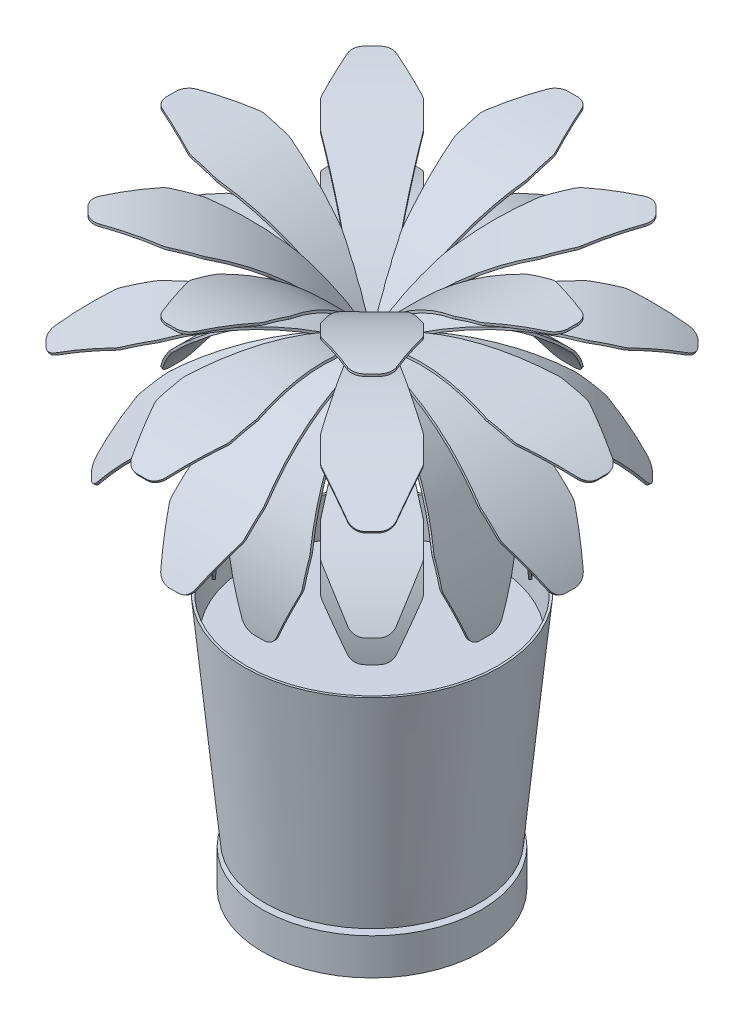
SolidWorks part; units mm, degrees
note: '?' marks a value the reader was unsure of.
material "Beech"
ref_plane "Front Plane" through (0, 0, 0) normal (0, 0, 1) x (1, 0, 0)
ref_plane "Top Plane" through (0, 0, 0) normal (0, 1, 0) x (1, 0, 0)
ref_plane "Right Plane" through (0, 0, 0) normal (1, 0, 0) x (0, 0, -1)
ref_axis "X-Axis" through (-88.99, 0, 0) along (1, 0, 0)?
ref_axis "Y-Axis" through (0, 55, 0) along (0, -1, 0)?
ref_axis "Z-Axis" through (0, 0, -88.99) along (0, 0, 1)?
sketch "Sketch1" plane through (0, 0, 0) normal (0, 0, 1) x (1, 0, 0)
  line L0 (0, 0) -> (0, 152.4)
  line L1 (87.3052, 177.8) -> (88.9, 177.8)
  line L2 (88.9, 177.8) -> (74.6125, 28.575)
  line L3 (74.6125, 28.575) -> (69.85, 28.575)
  line L4 (69.85, 28.575) -> (69.85, 25.4)
  line L5 (69.85, 25.4) -> (76.2, 25.4)
  line L6 (76.2, 25.4) -> (76.2, 0)
  line L7 (76.2, 0) -> (0, 0)
  line L8 (0, 0) -> (0, -76.2) construction
  line L9 (87.3052, 177.8) -> (84.8733, 152.4)
  line L10 (84.8733, 152.4) -> (0, 152.4)
  dimension "D1" = 25.4
  dimension "D2" = 177.8
  dimension "D3" = 152.4
  dimension "D4" = 6.35
  dimension "D5" = 3.175
  dimension "D6" = 1.5875
  dimension "D7" = 177.8
  dimension "D8" = 25.4
  dimension "D9" = 1.5875
revolve "Revolve1" add sketch "Sketch1" angle 360 about L8
sketch "Sketch3" plane through (0, 152.4, 0) normal (0, 1, 0) x (1, 0, 0)
  circle A0 centre (0, 0) radius 9.525
  dimension "D1" = 19.05
extrude "Boss-Extrude1" add sketch "Sketch3" along normal blind 177.8 draft 2 separate body
sketch "Sketch4" plane through (0, 0, 0) normal (0, 0, 1) x (1, 0, 0)
  line L0 (3.3161, 330.2) -> (-3.3161, 330.2) construction
  line L1 (77.1118, 190.5) -> (78.6993, 190.5)
  line L2 (0.846, 331.5433) -> (0, 330.2)
  line L3 (87.3052, 177.8) -> (-87.3052, 177.8) construction
  arc A0 (0, 330.2) -> (77.1118, 190.5) centre (-87.9882, 190.5) cw
  arc A1 (78.6993, 190.5) -> (0.846, 331.5433) centre (-87.9882, 190.5) ccw
  dimension "D2" = 165.1
  dimension "D1" = 1.5875
  dimension "D3" = 12.7
extrude "Boss-Extrude2" add sketch "Sketch4" along normal mid plane 50.8 separate body
sketch "Sketch5" plane through (0, 0, 0) normal (1, 0, 0) x (0, 0, -1)
  line L0 (-9.525, 190.5) -> (-25.4, 228.6)
  line L1 (-25.4, 331.5433) -> (-25.4, 190.5) construction
  line L2 (-25.4, 228.6) -> (-25.4, 247.65)
  line L3 (-25.4, 247.65) -> (-6.35, 331.5433)
  line L4 (-25.4, 331.5433) -> (25.4, 331.5433) construction
  line L5 (-6.35, 331.5433) -> (6.35, 331.5433)
  line L6 (6.35, 331.5433) -> (25.4, 247.65)
  line L7 (25.4, 190.5) -> (25.4, 331.5433) construction
  line L8 (25.4, 247.65) -> (25.4, 228.6)
  line L9 (25.4, 228.6) -> (9.525, 190.5)
  line L10 (-25.4, 190.5) -> (25.4, 190.5) construction
  line L11 (-9.525, 190.5) -> (9.525, 190.5)
  line L12 (0, 190.5) -> (0, 0) construction
  dimension "D1" = 19.05
  dimension "D2" = 19.05
  dimension "D3" = 38.1
  dimension "D4" = 12.7
extrude "Cut-Extrude1" cut sketch "Sketch5" along normal through all flip side to cut
fillet "Fillet6" radius 9.525 6 edges at (73.4711, 228.6, 25.4) (67.7505, 247.65, 25.4) (67.7505, 247.65, -25.4) (73.4711, 228.6, -25.4) (77.9056, 190.5, 9.525) (77.9056, 190.5, -9.525)
pattern_circular "CirPattern2" count 4 every 30 about axis through (0, 330.2, 0) along (0, 0, 1) of bodies 104
pattern_circular "CirPattern3" count 8 over 360 about axis through (0, 0, 0) along (0, 1, 0) of bodies 107 106 105 104
